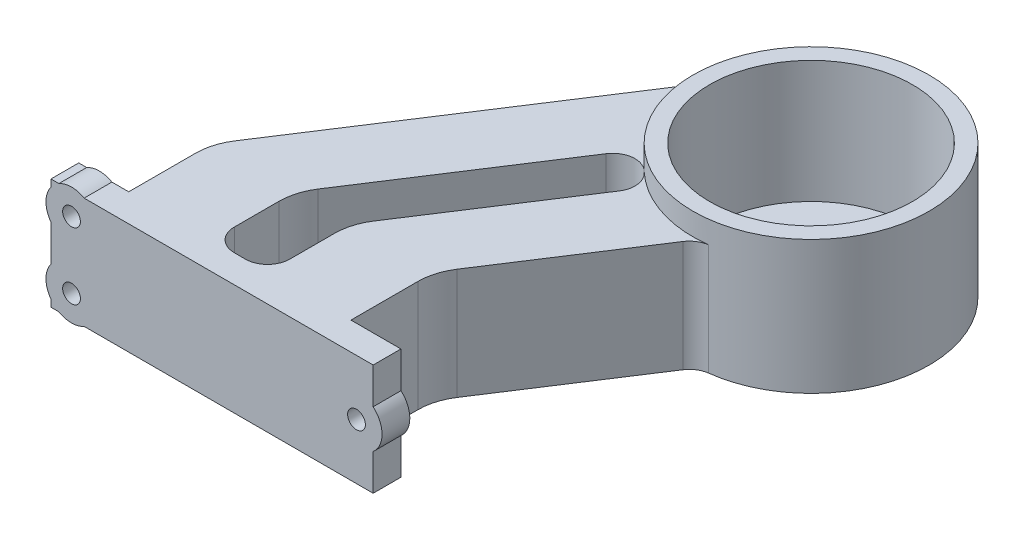
SolidWorks part; units mm, degrees
ref_plane "Front Plane" through (0, 0, 0) normal (0, 0, 1) x (1, 0, 0)
ref_plane "Top Plane" through (0, 0, 0) normal (0, 1, 0) x (1, 0, 0)
ref_plane "Right Plane" through (0, 0, 0) normal (1, 0, 0) x (0, 0, -1)
sketch "Sketch1" plane through (0, 0, 0) normal (0, 1, 0) x (1, 0, 0)
  circle A0 centre (0, 0) radius 18.25
  circle A1 centre (0, 0) radius 21.25
  circle A2 centre (0, 0) radius 11.5
  circle A3 centre (0, 0) radius 14 construction
  circle A4 centre (0, 14) radius 1.6
  circle A5 centre (14, 0) radius 1.6
  circle A6 centre (0, -14) radius 1.6
  circle A7 centre (-14, 0) radius 1.6
  point P18 (0, 0)
  dimension "D1" = 36.5
  dimension "D3" = 23
  dimension "D4" = 28
  dimension "D5" = 3.2
  dimension "D2" = 3
  dimension "D6" = 4
extrude "Boss-Extrude1" add sketch "Sketch1" along normal blind 2 contours A0 A7 A6 A5 A4 A2 region at (-17.7338, 0, 0)
extrude "Boss-Extrude2" add sketch "Sketch1<3>" along normal blind 24 contours A1 A0 region at (-20.649, 0, 0)
sketch "Sketch1<3>" plane through (0, 0, 0) normal (0, 1, 0) x (1, 0, 0) same geometry as "Sketch1"
sketch "Sketch2" plane through (0, 0, 0) normal (0, 1, 0) x (1, 0, 0)
  line L0 (-17.8202, 11.576) -> (-57.8202, -50)
  line L2 (-42.8202, -50) -> (-17.84, -11.5455)
  line L4 (-32.8202, -50) -> (-11.8141, -17.6632)
  line L6 (0.8674, -21.2323) -> (-17.8202, -50)
  line L7 (-57.8202, -50) -> (-57.8202, -70)
  line L8 (-57.8202, -70) -> (-42.8202, -70)
  line L9 (-42.8202, -70) -> (-42.8202, -50)
  line L10 (-32.8202, -50) -> (-32.8202, -70)
  line L11 (-32.8202, -70) -> (-17.8202, -70)
  line L12 (-17.8202, -70) -> (-17.8202, -50)
  circle A0 centre (0, 0) radius 21.25 construction
  circle A1 centre (0, 0) radius 21.25
  dimension "D1" = 15
  dimension "D3" = 40
  dimension "D4" = 10
  dimension "D5" = 20
extrude "Boss-Extrude3" add sketch "Sketch2" along normal blind 20 contours A1 L0 L2 | A1 L4 L6 region at (-39.9825, 0, 36.5409) region at (-19.5746, 0, 45.02)
sketch "Sketch3" plane through (0, 0, 70) normal (0, 0, 1) x (1, 0, 0)
  line L1 (-66.8202, 20) -> (-8.8202, 20)
  line L2 (-66.8202, 20) -> (-66.8202, 0)
  line L3 (-66.8202, 0) -> (-8.8202, 0)
  line L4 (-8.8202, 20) -> (-8.8202, 0)
  line L5 (-63.1184, 16) -> (-63.1184, 4) construction
  line L6 (-42.8202, 0) -> (-32.8202, 0) construction
  line L7 (-57.8202, 20) -> (-42.8202, 20) construction
  circle A0 centre (-37.8202, 10) radius 26 construction
  circle A1 centre (-11.8202, 10) radius 1.6
  circle A2 centre (-63.1184, 16) radius 1.6
  circle A3 centre (-63.1184, 4) radius 1.6
  circle A4 centre (-63.1184, 16) radius 4.6
  circle A5 centre (-63.1184, 4) radius 4.6
  circle A6 centre (-11.8202, 10) radius 4.6
  point P9 (-66.8202, 10)
  point P23 (-37.8202, 0)
  point P24 (-37.8202, 0)
  dimension "D1" = 52
  dimension "D2" = 3.2
  dimension "D3" = 58
  dimension "D4" = 12
  dimension "D5" = 3
extrude "Boss-Extrude4" add sketch "Sketch3" against normal blind 5 contours A6 L4 L1 L3 | L4 A6 A1 | L4 A6 | A5 A4 L2 | A5 A4 | A4 L1 L2 A2 | A5 L2 L3 A3 | A4 | A4 L1 | L1 A4 | A4 L1 L2 | L2 A4 | L2 A5 | A5 L2 L3 | A5 L3 | A5 region at (-66.3783, 19.6068, 70) region at (-63.1184, 20.2414, 70) region at (-63.1184, 19.8805, 70) region at (-67.1826, 16, 70) region at (-36.1624, 10, 70) region at (-61.7184, 8.2561, 70) region at (-67.1826, 4, 70) region at (-8.1695, 10, 70) region at (-8.9395, 10, 70) region at (-66.3783, 0.3932, 70) region at (-63.1184, -0.2414, 70)
fillet "Fillet3" radius 10 4 edges at (-57.8202, 10, 50) (-32.8202, 10, 50) (-42.8202, 10, 50) (-17.8202, 10, 50)
fillet "Fillet4" radius 4 5 edges at (-42.8202, 10, 65) (-32.8202, 10, 65) (-17.84, 10, 11.5455) (0.8674, 10, 21.2323) (-11.8141, 10, 17.6632)
mirror "Mirror1" [suppressed] of bodies 104
delete or keep bodies "Body-Delete/Keep 1" [suppressed] type delete bodies bodies 104
